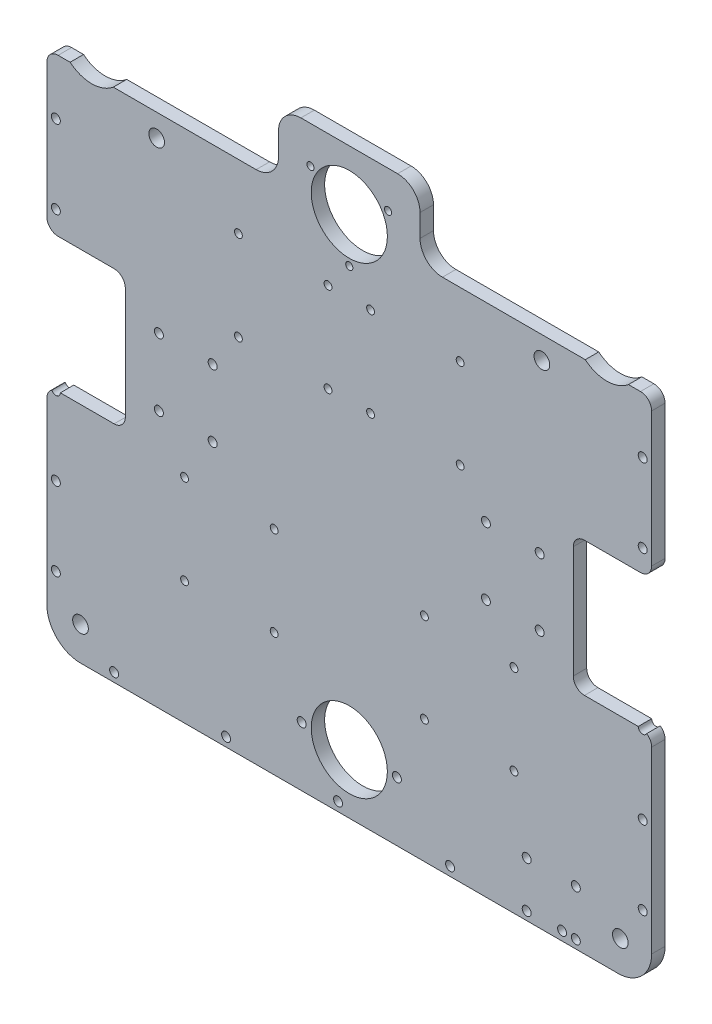
SolidWorks part; units mm, degrees
material "Alumina"
ref_plane "Front Plane" through (0, 0, 0) normal (0, 0, 1) x (1, 0, 0)
ref_plane "Top Plane" through (0, 0, 0) normal (0, 1, 0) x (1, 0, 0)
ref_plane "Right Plane" through (0, 0, 0) normal (1, 0, 0) x (0, 0, -1)
sketch "Sketch1" plane through (0, 0, 0) normal (0, 0, 1) x (1, 0, 0)
  line L1 (-135, 130) -> (135, 130)
  line L2 (-135, 130) -> (-135, -130)
  line L3 (-135, -130) -> (135, -130)
  line L4 (135, 130) -> (135, -130)
  line L5 (-135, 130) -> (135, -130) construction
  line L6 (-135, -130) -> (135, 130) construction
  point P0 (0, 0)
  dimension "D1" = 270
  dimension "D2" = 260
extrude "Boss-Extrude1" add sketch "Sketch1" along normal blind 6
sketch "Sketch2" plane through (0, 0, 6) normal (0, 0, 1) x (1, 0, 0)
  line L0 (-135, 130) -> (-135, -130) construction
  line L1 (-135, 30) -> (-100, 30)
  line L2 (-135, 30) -> (-135, -30)
  line L3 (-135, -30) -> (-100, -30)
  line L4 (-100, 30) -> (-100, -30)
  line L5 (-135, 30) -> (-100, -30) construction
  line L6 (-135, -30) -> (-100, 30) construction
  circle A0 centre (-85, 15) radius 2
  circle A1 centre (-61, 15) radius 2
  circle A2 centre (-61, -15) radius 2
  circle A3 centre (-85, -15) radius 2
  point P0 (-117.5, 0)
  dimension "D3" = 4
  dimension "D4" = 24
  dimension "D5" = 30
  dimension "D6" = 50
  dimension "D1" = 35
  dimension "D2" = 60
extrude "Cut-Extrude1" cut sketch "Sketch2" against normal through all
sketch "Sketch3" plane through (0, 0, 6) normal (0, 0, 1) x (1, 0, 0)
  line L1 (0, -103.5) -> (0, -83.5) construction
  line L2 (0, -103.5) -> (17.3205, -113.5) construction
  line L3 (0, -103.5) -> (-17.3205, -113.5) construction
  circle A3 centre (0, -103.5) radius 17
  dimension "D2" = 34
  dimension "D4" = 120
  dimension "D5" = 120
  dimension "D6" = 20
extrude "Cut-Extrude2" cut sketch "Sketch3" against normal through all
mirror "Mirror1" about plane through (0, 0, 0) normal (1, 0, 0) of "Cut-Extrude1"
mirror "Mirror2" about plane through (0, 0, 0) normal (0, 1, 0) of "Cut-Extrude2"
sketch "Sketch4" plane through (0, 0, 6) normal (0, 0, 1) x (1, 0, 0)
  circle A0 centre (21.25, -103.5) radius 2
  circle A1 centre (-21.25, -103.5) radius 2
  dimension "D1" = 4
extrude "Cut-Extrude3" cut sketch "Sketch4" against normal through all
sketch "Sketch5" plane through (0, 0, 6) normal (0, 0, 1) x (1, 0, 0)
  circle A0 centre (79.2065, -126.2348) radius 2
  circle A1 centre (79.2065, -105.7652) radius 2
  circle A2 centre (101.1382, -105.7652) radius 2
  circle A3 centre (101.1382, -126.2348) radius 2
  dimension "D1" = 4
extrude "Cut-Extrude4" cut sketch "Sketch5" against normal through all
fillet "Fillet1" radius 15 4 edges at (135, 130, 3) (-135, 130, 3) (-135, -130, 3) (135, -130, 3)
sketch "Sketch6" plane through (0, 0, 6) normal (0, 0, 1) x (1, 0, 0)
  circle A0 centre (-115, 115) radius 12.5
  dimension "D1" = 25
extrude "Cut-Extrude5" cut sketch "Sketch6" against normal through all
sketch "Sketch8" plane through (0, 0, 6) normal (0, 0, 1) x (1, 0, 0)
  circle A0 centre (49.5, 31.3) radius 1.75
  circle A1 centre (9.5, 31.3) radius 1.75
  circle A2 centre (9.5, 71.3) radius 1.75
  circle A3 centre (49.5, 71.3) radius 1.75
  circle A4 centre (-49.5, 31.3) radius 1.75
  circle A5 centre (-9.5, 31.3) radius 1.75
  circle A6 centre (-49.5, 71.3) radius 1.75
  circle A7 centre (-9.5, 71.3) radius 1.75
  dimension "D1" = 3.5
extrude "Cut-Extrude6" cut sketch "Sketch8" against normal through all
sketch "Sketch9" plane through (0, 0, 6) normal (0, 0, 1) x (1, 0, 0)
  circle A0 centre (115, 111.5) radius 12.5
  dimension "D1" = 25
extrude "Cut-Extrude7" cut sketch "Sketch9" against normal through all
sketch "Sketch10" plane through (0, 0, 6) normal (0, 0, 1) x (1, 0, 0)
  line L0 (135, 30) -> (135, 115) construction
  line L1 (135, 100) -> (31.5934, 100)
  line L2 (135, 100) -> (135, 130)
  line L3 (135, 130) -> (31.5934, 130)
  line L4 (31.5934, 100) -> (31.5934, 130)
  line L5 (120, 130) -> (-120, 130) construction
  dimension "D1" = 30
extrude "Cut-Extrude8" cut sketch "Sketch10" against normal through all
ref_plane "Plane1" through (0, 0, 0) normal (-1, 0, 0) x (0, 0, 1)
fillet "Fillet2" radius 10 2 edges at (31.5934, 130, 3) (31.5934, 100, 3)
mirror "Mirror3" about plane through (0, 0, 0) normal (-1, 0, 0) of "Cut-Extrude8", "Fillet2"
sketch "Sketch11" plane through (0, 0, 6) normal (0, 0, 1) x (1, 0, 0)
  circle A0 centre (-17.3205, 113.5) radius 1.6
  circle A1 centre (17.3205, 113.5) radius 1.6
  circle A2 centre (0, 83.5) radius 1.6
  circle A3 centre (86, 90) radius 3.5
  circle A4 centre (-86, 90) radius 3.5
  circle A5 centre (121, -116) radius 3.5
  circle A6 centre (-120, -115) radius 3.5
  dimension "D1" = 3.2
  dimension "D2" = 7
extrude "Cut-Extrude9" cut sketch "Sketch11" against normal through all
sketch "Sketch12" plane through (0, 0, 6) normal (0, 0, 1) x (1, 0, 0)
  circle A0 centre (115, 111.5) radius 15
  circle A1 centre (-115, 111.5) radius 15
  dimension "D1" = 30
  dimension "D2" = 30
extrude "Cut-Extrude10" cut sketch "Sketch12" against normal through all
fillet "Fillet3" radius 5 2 edges at (135, 100, 3) (-135, 100, 3)
fillet "Fillet4" radius 5 8 edges at (135, 30, 3) (100, 30, 3) (100, -30, 3) (135, -30, 3) (-135, -30, 3) (-100, -30, 3) (-100, 30, 3) (-135, 30, 3)
sketch "Sketch13" plane through (0, 0, 6) normal (0, 0, 1) x (1, 0, 0)
  line L0 (0, 3.3) -> (0, -3.3) construction
  line L1 (-120, -130) -> (120, -130) construction
  line L2 (-135, -35) -> (-135, -115) construction
  circle A0 centre (33.5446, -34.9403) radius 1.75
  circle A1 centre (73.5446, -34.9403) radius 1.75
  circle A2 centre (73.5446, -74.9403) radius 1.75
  circle A3 centre (33.5446, -74.9403) radius 1.75
  circle A4 centre (-33.5446, -74.9403) radius 1.75
  circle A5 centre (-73.5446, -74.9403) radius 1.75
  circle A6 centre (-73.5446, -34.9403) radius 1.75
  circle A7 centre (-33.5446, -34.9403) radius 1.75
  circle A8 centre (-131, -100) radius 2
  circle A9 centre (-131, -65) radius 2
  circle A10 centre (-131, -30) radius 2
  circle A11 centre (-131, 5) radius 2
  circle A12 centre (-131, 40) radius 2
  circle A13 centre (-131, 75) radius 2
  circle A14 centre (-105, -126) radius 2
  circle A15 centre (-55, -126) radius 2
  circle A16 centre (-5, -126) radius 2
  circle A17 centre (45, -126) radius 2
  circle A18 centre (95, -126) radius 2
  circle A19 centre (145, -126) radius 2
  circle A20 centre (195, -126) radius 2
  circle A21 centre (245, -126) radius 2
  circle A22 centre (295, -126) radius 2
  circle A23 centre (345, -126) radius 2
  circle A24 centre (395, -126) radius 2
  circle A25 centre (445, -126) radius 2
  circle A26 centre (495, -126) radius 2
  circle A28 centre (131, 75) radius 2
  circle A29 centre (131, 40) radius 2
  circle A30 centre (131, 5) radius 2
  circle A31 centre (131, -30) radius 2
  circle A32 centre (131, -65) radius 2
  circle A33 centre (131, -100) radius 2
  dimension "D1" = 3.5
  dimension "D5" = 30
  dimension "D6" = 4
  dimension "D9" = 4
  dimension "D2" = 40
  dimension "D3" = 40
  dimension "D4" = 40
  dimension "D7" = 4
  dimension "D10" = 4
  dimension "D11" = 30
  dimension "D8" = 6
  dimension "D12" = 13
extrude "Cut-Extrude11" cut sketch "Sketch13" against normal through all
